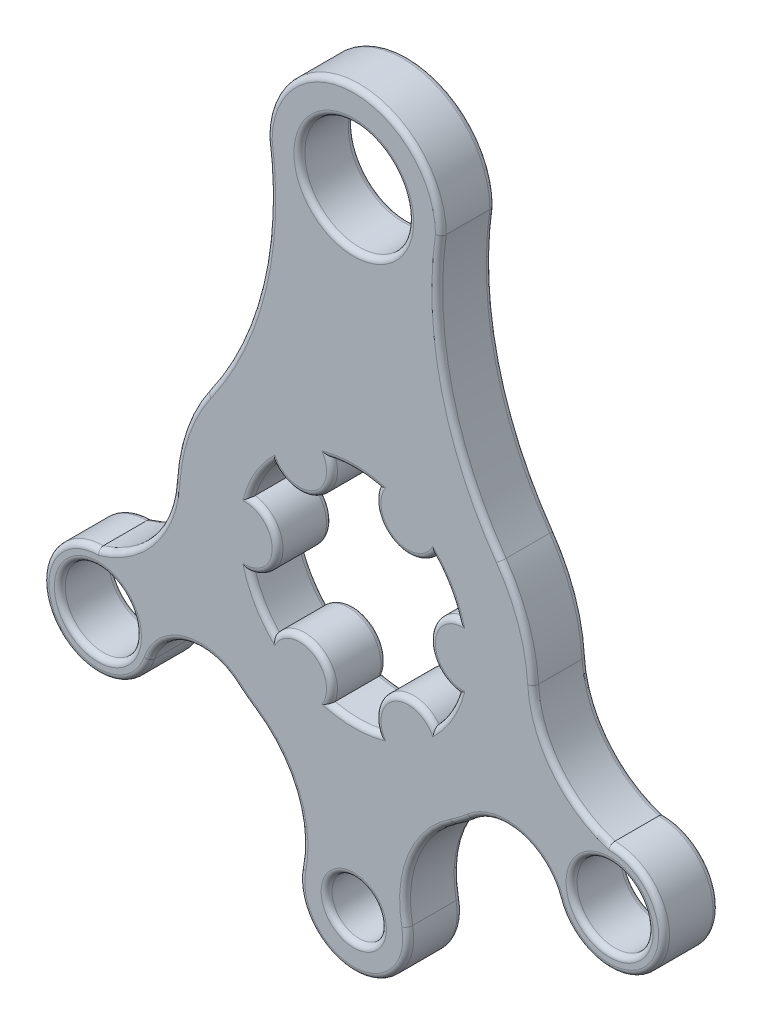
SolidWorks part; units mm, degrees
ref_plane "Front Plane" through (0, 0, 0) normal (0, 0, 1) x (1, 0, 0)
ref_plane "Top Plane" through (0, 0, 0) normal (0, 1, 0) x (1, 0, 0)
ref_plane "Right Plane" through (0, 0, 0) normal (1, 0, 0) x (0, 0, -1)
sketch "Sketch2" plane through (0, 0, 0) normal (0, 0, 1) x (1, 0, 0)
  line L0 (0, 0) -> (0, 89.9249) construction
  arc A0 (-14.6874, 13.575) -> (-19.1, 5.9321) centre (0, 0) ccw
  arc A1 (-19.1, -5.9321) -> (-19.1, 5.9321) centre (-20, 0) ccw
  arc A2 (-14.6874, 13.575) -> (-4.4126, 19.5071) centre (-10, 17.3205) ccw
  arc A3 (4.4126, 19.5071) -> (14.6874, 13.575) centre (10, 17.3205) ccw
  arc A4 (19.1, 5.9321) -> (19.1, -5.9321) centre (20, 0) ccw
  arc A5 (14.6874, -13.575) -> (4.4126, -19.5071) centre (10, -17.3205) ccw
  arc A6 (-4.4126, -19.5071) -> (-14.6874, -13.575) centre (-10, -17.3205) ccw
  arc A7 (-19.1, -5.9321) -> (-14.6874, -13.575) centre (0, 0) ccw
  arc A8 (-4.4126, -19.5071) -> (4.4126, -19.5071) centre (0, 0) ccw
  arc A9 (14.6874, -13.575) -> (19.1, -5.9321) centre (0, 0) ccw
  arc A10 (19.1, 5.9321) -> (14.6874, 13.575) centre (0, 0) ccw
  arc A11 (4.4126, 19.5071) -> (-4.4126, 19.5071) centre (0, 0) ccw
  circle A12 centre (0, 65) radius 10
  arc A13 (15.5763, 61.3421) -> (-15.5763, 61.3421) centre (0, 65) ccw
  arc A14 (-16, 65) -> (-26.9908, 18.9867) centre (-79.3367, 55.8094) cw
  arc A15 (-26.9908, 18.9867) -> (-32.9432, 1.9347) centre (0, 0) ccw
  circle A16 centre (-47, -26) radius 7
  arc A17 (-47, -16) -> (-37.5509, -29.2733) centre (-47, -26) ccw
  circle A18 centre (0, -50) radius 5
  arc A19 (-9.804, -48.03) -> (9.804, -48.03) centre (0, -50) ccw
  arc A20 (47, -16) -> (37.5509, -29.2733) centre (47, -26) cw
  circle A21 centre (47, -26) radius 7
  arc A22 (-47, -16) -> (-32.9432, 1.9347) centre (-52.9088, 3.1072) ccw
  arc A23 (47, -16) -> (32.9432, 1.9347) centre (52.9088, 3.1072) cw
  arc A24 (16, 65) -> (26.9908, 18.9867) centre (79.3367, 55.8094) ccw
  arc A25 (37.5509, -29.2733) -> (21.5665, -24.9777) centre (28.1018, -32.5467) ccw
  arc A26 (9.804, -48.03) -> (18.3132, -27.4523) centre (29.4121, -44.09) cw
  arc A27 (-9.804, -48.03) -> (-18.3132, -27.4523) centre (-29.4121, -44.09) ccw
  arc A28 (-37.5509, -29.2733) -> (-21.5665, -24.9777) centre (-28.1018, -32.5467) cw
  arc A29 (32.9432, 1.9347) -> (26.9908, 18.9867) centre (0, 0) ccw
  arc A30 (-21.5665, -24.9777) -> (-18.3132, -27.4523) centre (0, 0) ccw
  arc A31 (18.3132, -27.4523) -> (21.5665, -24.9777) centre (0, 0) ccw
  point P17 (0, 0)
  dimension "D1" = 40
  dimension "D2" = 12
  dimension "D4" = 20
  dimension "D5" = 32
  dimension "D7" = 64
  dimension "D8" = 66
  dimension "D9" = 14
  dimension "D10" = 20
  dimension "D12" = 20
  dimension "D13" = 10
  dimension "D16" = 20
  dimension "D17" = 10
  dimension "D18" = 20
  dimension "D6" = 65
  dimension "D11" = 26
  dimension "D14" = 24
  dimension "D15" = 47
  dimension "D3" = 6
extrude "Boss-Extrude1" add sketch "Sketch2" along normal mid plane 10 contours A11 A3 A10 A4 A9 A5 A8 A6 A7 A1 A0 A2 A12 A13 A14 A15 A22 A17 A28 A30 A27 A19 A26 A31 A25 A20 A23 A29 A24 A21 A16 region at (15.7906, 38.6841, 0)
fillet "Fillet1" radius 1 64 edges at (-7, 12.1244, 5) (-17.3205, 10, 5) (-14, 0, 5) (-17.3205, -10, 5) (-7, -12.1244, 5) (0, -20, 5) (7, -12.1244, 5) (17.3205, -10, 5) (14, 0, 5) (17.3205, 10, 5) (7, 12.1244, 5) (0, 20, 5) (-40, -26, 5) (5, -50, 5) (54, -26, 5) (31.1563, 10.8758, 5) (37.1677, -9.2303, 5) (55.1466, -31.7994, 5) (30.6971, -22.8893, 5) (19.9782, -26.2654, 5) (10.9299, -36.4474, 5) (0, -60, 5) (-10.9299, -36.4474, 5) (-19.9782, -26.2654, 5) (-30.6971, -22.8893, 5) (-55.1466, -31.7994, 5) (-37.1677, -9.2303, 5) (-31.1563, 10.8758, 5) (-17.0878, 40.9406, 5) (0, 81, 5) (17.0878, 40.9406, 5) (10, 65, 5) (7, 12.1244, -5) (17.3205, 10, -5) (14, 0, -5) (17.3205, -10, -5) (7, -12.1244, -5) (0, -20, -5) (-7, -12.1244, -5) (-17.3205, -10, -5) (-14, 0, -5) (-17.3205, 10, -5) (-7, 12.1244, -5) (0, 20, -5) (-40, -26, -5) (5, -50, -5) (54, -26, -5) (0, 81, -5) (-17.0878, 40.9406, -5) (-31.1563, 10.8758, -5) (-37.1677, -9.2303, -5) (-55.1466, -31.7994, -5) (-30.6971, -22.8893, -5) (-19.9782, -26.2654, -5) (-10.9299, -36.4474, -5) (0, -60, -5) (10.9299, -36.4474, -5) (19.9782, -26.2654, -5) (30.6971, -22.8893, -5) (55.1466, -31.7994, -5) (37.1677, -9.2303, -5) (31.1563, 10.8758, -5) (17.0878, 40.9406, -5) (10, 65, -5)
